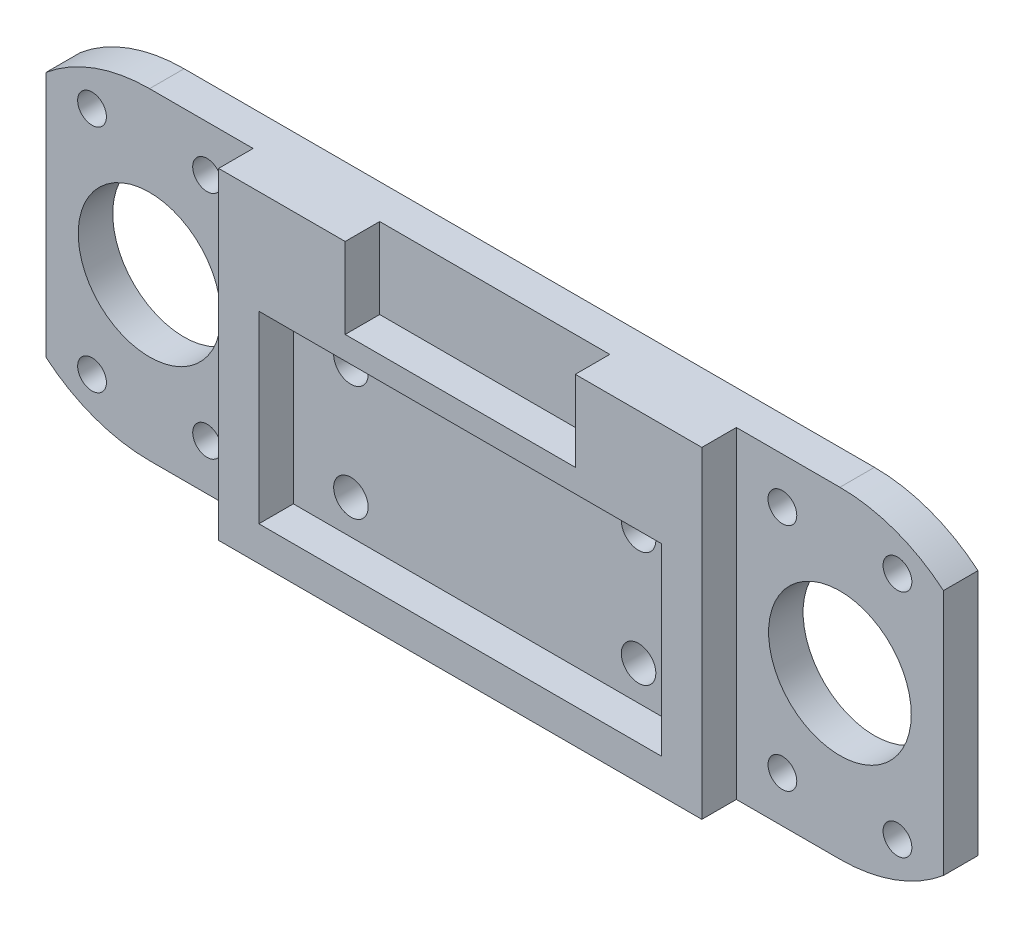
SolidWorks part; units mm, degrees
ref_plane "Front Plane" through (0, 0, 0) normal (0, 0, 1) x (1, 0, 0)
ref_plane "Top Plane" through (0, 0, 0) normal (0, 1, 0) x (1, 0, 0)
ref_plane "Right Plane" through (0, 0, 0) normal (1, 0, 0) x (0, 0, -1)
sketch "Sketch1" plane through (0, 0, 0) normal (0, 0, 1) x (1, 0, 0)
  line L0 (-39, 10.7238) -> (-39, -10.7238)
  line L1 (-30, -14) -> (30, -14)
  line L3 (-35, 10) -> (-25, -10) construction
  line L4 (-35, -10) -> (-25, 10) construction
  line L5 (-30, 14) -> (30, 14)
  line L6 (-30, 0) -> (30, 0) construction
  line L7 (39, 10.7238) -> (39, -10.7238)
  line L8 (25, 10) -> (35, -10) construction
  line L9 (35, 10) -> (25, -10) construction
  arc A0 (-30, 14) -> (-39, 10.7238) centre (-30, 0) ccw
  arc A1 (-39, -10.7238) -> (-30, -14) centre (-30, 0) ccw
  circle A2 centre (-30, 0) radius 6.2
  circle A3 centre (-35, 10) radius 1.25
  circle A4 centre (-25, 10) radius 1.25
  circle A5 centre (-35, -10) radius 1.25
  circle A6 centre (-25, -10) radius 1.25
  arc A7 (30, -14) -> (39, -10.7238) centre (30, 0) ccw
  arc A8 (39, 10.7238) -> (30, 14) centre (30, 0) ccw
  circle A9 centre (30, 0) radius 6.2
  circle A10 centre (25, 10) radius 1.25
  circle A11 centre (35, 10) radius 1.25
  circle A12 centre (25, -10) radius 1.25
  circle A13 centre (35, -10) radius 1.25
  point P7 (0, 0)
  point P8 (0, 0)
  point P18 (-30, 0)
  point P25 (30, 0)
  point P36 (30, 0)
  dimension "D2" = 14
  dimension "D3" = 12.4
  dimension "D6" = 2.5
  dimension "D8" = 2.5
  dimension "D11" = 28
  dimension "D4" = 20
  dimension "D5" = 10
  dimension "D7" = 60
  dimension "D9" = 10
  dimension "D10" = 20
  dimension "D16" = 9
extrude "Main" add sketch "Sketch1" along normal mid plane 3
sketch "Sketch2" plane through (0, 0, 1.5) normal (0, 0, -1) x (-1, 0, 0)
  line L0 (30, -14) -> (-30, -14) construction
  line L1 (39, 10.7238) -> (39, -10.7238) construction
  line L2 (21, 14) -> (10, 14)
  line L3 (21, 14) -> (21, -14)
  line L4 (21, -14) -> (-21, -14)
  line L5 (-21, 14) -> (-21, -14)
  line L6 (17.5, 5) -> (-17.5, 5)
  line L7 (17.5, 5) -> (17.5, -11)
  line L8 (17.5, -11) -> (-17.5, -11)
  line L9 (-17.5, 5) -> (-17.5, -11)
  line L10 (-39, -10.7238) -> (-39, 10.7238) construction
  line L11 (-30, 14) -> (30, 14) construction
  line L12 (-39, -10.7238) -> (-39, 10.7238) construction
  line L13 (-30, 14) -> (30, 14) construction
  line L14 (10, 14) -> (10, 7)
  line L15 (10, 7) -> (-10, 7)
  line L16 (-10, 7) -> (-10, 14)
  line L17 (-10, 14) -> (-21, 14)
  point P14 (0, 7)
  point P22 (0, 5)
  point P27 (17.5, -3)
  dimension "D1" = 16
  dimension "D2" = 3.5
  dimension "D3" = 18
  dimension "D4" = 7
  dimension "D5" = 35
  dimension "D6" = 78
  dimension "D7" = 18
  dimension "D8" = 3.5
  dimension "D9" = 3
  dimension "D10" = 2
  dimension "D11" = 20
  dimension "D12" = 3
extrude "Framework" add sketch "Sketch2" against normal blind 3
sketch "Sketch3" plane through (0, 0, -1.5) normal (0, 0, -1) x (-1, 0, 0)
  line L6 (17.5, 5) -> (17.5, -11) construction
  line L9 (17.5, -11) -> (-17.5, -11) construction
  circle A1 centre (12.5, -8) radius 1.5
  point P0 (17.5, -3)
  dimension "D1" = 3
  dimension "D2" = 5
  dimension "D3" = 12.5
  dimension "D4" = 8
  dimension "D5" = 5
  dimension "D6" = 3
extrude "FixHole" cut sketch "Sketch3" against normal through all
pattern_linear "HolePattern" count 2 spacing 25 along (1, 0, 0) count 2 spacing 10 along (0, 1, 0) of "FixHole"
